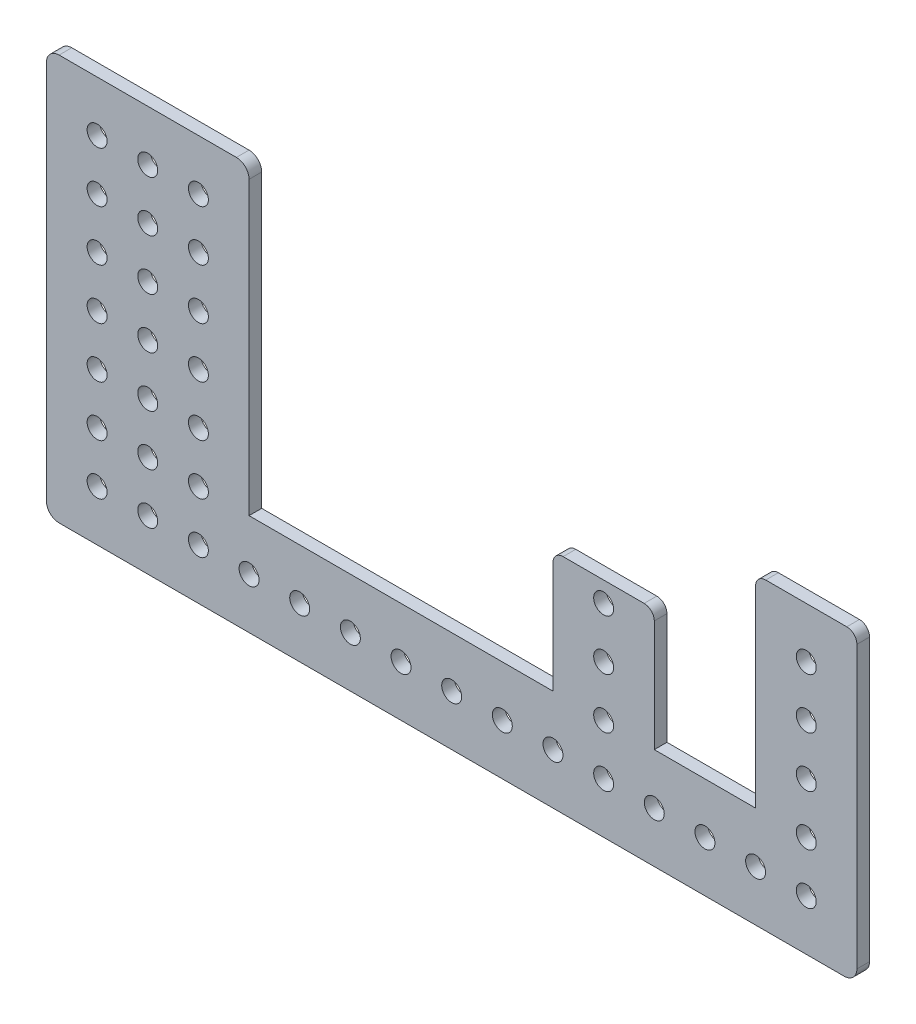
SolidWorks part; units mm, degrees
ref_plane "Front Plane" through (0, 0, 0) normal (0, 0, 1) x (1, 0, 0)
ref_plane "Top Plane" through (0, 0, 0) normal (0, 1, 0) x (1, 0, 0)
ref_plane "Right Plane" through (0, 0, 0) normal (1, 0, 0) x (0, 0, -1)
sketch "Sketch1" plane through (0, 0, 0) normal (0, 0, 1) x (1, 0, 0)
  line L0 (99.0226, -20.0767) -> (102.1976, -20.0767)
  line L1 (-101.0024, -20.0767) -> (99.0226, -20.0767)
  line L2 (-101.0024, -20.0767) -> (-101.0024, -42.3017)
  line L3 (-97.8274, -45.4767) -> (99.0226, -45.4767)
  line L4 (102.1976, 2.1483) -> (102.1976, -42.3017)
  line L6 (-101.0024, -20.0767) -> (-101.0024, 52.9483)
  line L7 (-97.8274, 56.1233) -> (-53.3774, 56.1233)
  line L8 (-50.2024, -20.0767) -> (-50.2024, 52.9483)
  line L9 (102.1976, -20.0767) -> (102.1976, 2.1483)
  arc A0 (-101.0024, -42.3017) -> (-97.8274, -45.4767) centre (-97.8274, -42.3017) ccw
  arc A1 (99.0226, -45.4767) -> (102.1976, -42.3017) centre (99.0226, -42.3017) ccw
  arc A3 (-53.3774, 56.1233) -> (-50.2024, 52.9483) centre (-53.3774, 52.9483) cw
  arc A4 (-101.0024, 52.9483) -> (-97.8274, 56.1233) centre (-97.8274, 52.9483) cw
  point P11 (-101.0024, -45.4767)
  point P14 (102.1976, -45.4767)
  point P17 (102.1976, -20.0767)
  point P20 (-50.2024, 56.1233)
  point P23 (-101.0024, 56.1233)
  dimension "D5" = 3.175
  dimension "D1" = 25.4
  dimension "D2" = 203.2
  dimension "D3" = 50.8
  dimension "D4" = 76.2
extrude "Boss-Extrude1" add sketch "Sketch1" along normal blind 3.175 contours L1 L8 L7 L6 | L4 L1 L2 L3 region at (0.5976, -32.7667, 0) region at (-75.6024, 17.9814, 0)
sketch "Sketch3" plane through (0, 0, 3.175) normal (0, 0, 1) x (1, 0, 0)
  line L0 (-50.2024, -20.0767) -> (102.1976, -20.0767) construction
  line L1 (48.8576, 10.4033) -> (28.5376, 10.4033)
  line L2 (51.3976, 7.8633) -> (51.3976, -20.0767)
  line L3 (51.3976, -20.0767) -> (25.9976, -20.0767)
  line L4 (25.9976, 7.8633) -> (25.9976, -20.0767)
  line L6 (79.3376, 30.7233) -> (99.6576, 30.7233)
  line L7 (76.7976, 28.1833) -> (76.7976, -20.0767)
  line L8 (76.7976, -20.0767) -> (102.1976, -20.0767)
  line L9 (102.1976, 28.1833) -> (102.1976, -20.0767)
  line L10 (-50.2024, -20.0767) -> (-50.2024, 52.9483) construction
  arc A0 (99.6576, 30.7233) -> (102.1976, 28.1833) centre (99.6576, 28.1833) cw
  arc A1 (79.3376, 30.7233) -> (76.7976, 28.1833) centre (79.3376, 28.1833) ccw
  arc A2 (28.5376, 10.4033) -> (25.9976, 7.8633) centre (28.5376, 7.8633) ccw
  arc A3 (48.8576, 10.4033) -> (51.3976, 7.8633) centre (48.8576, 7.8633) cw
  point P14 (102.1976, 30.7233)
  point P17 (76.7976, 30.7233)
  point P20 (25.9976, 10.4033)
  point P23 (51.3976, 10.4033)
  dimension "D7" = 2.54
  dimension "D1" = 30.48
  dimension "D2" = 76.2
  dimension "D3" = 25.4
  dimension "D4" = 25.4
  dimension "D5" = 25.4
  dimension "D6" = 50.8
extrude "Boss-Extrude2" add sketch "Sketch3" against normal up to surface (3.175 mm away) up to face at (-24.8024, 0.2433, 0)
sketch "Sketch4" plane through (0, 0, 3.175) normal (0, 0, 1) x (1, 0, 0)
  line L0 (-101.0024, -42.3017) -> (-101.0024, 52.9483) construction
  line L1 (-97.8274, -45.4767) -> (99.0226, -45.4767) construction
  line L2 (51.3976, -20.0767) -> (51.3976, 7.8633) construction
  line L3 (102.1976, 28.1833) -> (102.1976, -42.3017) construction
  line L4 (-97.8274, 56.1233) -> (-53.3774, 56.1233) construction
  line L5 (76.7976, 28.1833) -> (76.7976, -20.0767) construction
  circle A0 centre (-88.3024, -32.7767) radius 2.5
  circle A1 centre (-75.6024, -32.7767) radius 2.5
  circle A2 centre (-62.9024, -32.7767) radius 2.5
  circle A3 centre (-50.2024, -32.7767) radius 2.5
  circle A4 centre (-37.5024, -32.7767) radius 2.5
  circle A5 centre (-24.8024, -32.7767) radius 2.5
  circle A6 centre (-12.1024, -32.7767) radius 2.5
  circle A7 centre (0.5976, -32.7767) radius 2.5
  circle A8 centre (13.2976, -32.7767) radius 2.5
  circle A9 centre (25.9976, -32.7767) radius 2.5
  circle A10 centre (38.6976, -32.7767) radius 2.5
  circle A11 centre (51.3976, -32.7767) radius 2.5
  circle A12 centre (64.0976, -32.7767) radius 2.5
  circle A13 centre (76.7976, -32.7767) radius 2.5
  circle A14 centre (89.4976, -32.7767) radius 2.5
  circle A15 centre (38.6976, -20.0767) radius 2.5
  circle A16 centre (89.4976, -20.0767) radius 2.5
  circle A17 centre (-88.3024, 43.4233) radius 2.5
  circle A18 centre (-75.6024, 43.4233) radius 2.5
  circle A19 centre (-62.9024, 43.4233) radius 2.5
  circle A20 centre (-75.6024, 30.7233) radius 2.5
  circle A21 centre (-62.9024, 30.7233) radius 2.5
  circle A22 centre (-75.6024, 18.0233) radius 2.5
  circle A23 centre (-62.9024, 18.0233) radius 2.5
  circle A24 centre (-75.6024, 5.3233) radius 2.5
  circle A25 centre (-62.9024, 5.3233) radius 2.5
  circle A26 centre (-75.6024, -7.3767) radius 2.5
  circle A27 centre (-62.9024, -7.3767) radius 2.5
  circle A28 centre (-75.6024, -20.0767) radius 2.5
  circle A29 centre (-62.9024, -20.0767) radius 2.5
  circle A30 centre (-88.3024, 30.7233) radius 2.5
  circle A31 centre (-88.3024, 18.0233) radius 2.5
  circle A32 centre (-88.3024, 5.3233) radius 2.5
  circle A33 centre (-88.3024, -7.3767) radius 2.5
  circle A34 centre (-88.3024, -20.0767) radius 2.5
  circle A36 centre (38.6976, -7.3767) radius 2.5
  circle A37 centre (89.4976, -7.3767) radius 2.5
  circle A39 centre (38.6976, 5.3233) radius 2.5
  circle A40 centre (89.4976, 5.3233) radius 2.5
  circle A44 centre (-88.3024, 56.1233) radius 2.5 [skipped]
  circle A45 centre (-88.3024, 68.8233) radius 2.5 [skipped]
  circle A46 centre (89.4976, 18.0233) radius 2.5
  dimension "D1" = 5
  dimension "D5" = 5
  dimension "D8" = 5
  dimension "D11" = 5
  dimension "D17" = 5
  dimension "D2" = 12.7
  dimension "D3" = 12.7
  dimension "D6" = 25.4
  dimension "D7" = 12.7
  dimension "D9" = 12.7
  dimension "D10" = 25.4
  dimension "D12" = 12.7
  dimension "D13" = 12.7
  dimension "D18" = 12.7
  dimension "D19" = 12.7
  dimension "D4" = 15
  dimension "D14" = 3
  dimension "D15" = 6
  dimension "D16" = 3
extrude "Cut-Extrude1" cut sketch "Sketch4" against normal through all
